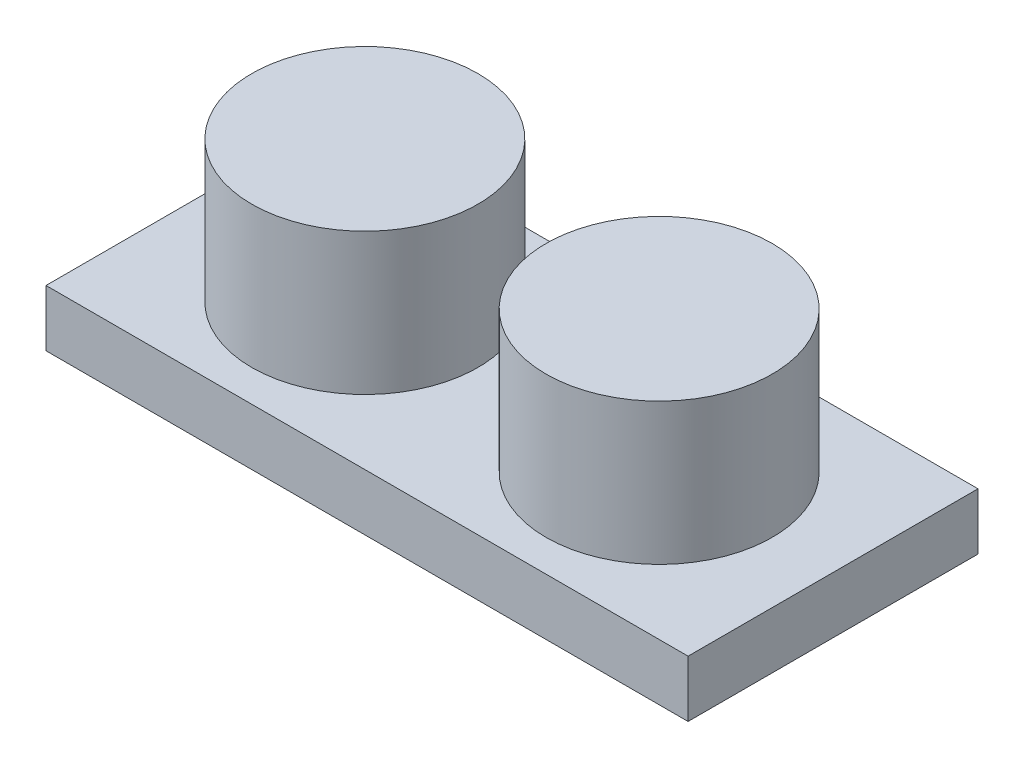
SolidWorks part; units mm, degrees
ref_plane "前基準面" through (0, 0, 0) normal (0, 0, 1) x (1, 0, 0)
ref_plane "上基準面" through (0, 0, 0) normal (0, 1, 0) x (1, 0, 0)
ref_plane "右基準面" through (0, 0, 0) normal (1, 0, 0) x (0, 0, -1)
sketch "草圖1" plane through (0, 0, 0) normal (0, 1, 0) x (1, 0, 0)
  line L0 (0, 10.25) -> (0, -10.25) construction
  line L1 (-22.7, 10.25) -> (22.7, 10.25)
  line L2 (-22.7, 10.25) -> (-22.7, -10.25)
  line L3 (-22.7, -10.25) -> (22.7, -10.25)
  line L4 (22.7, 10.25) -> (22.7, -10.25)
  line L5 (-22.7, 10.25) -> (22.7, -10.25) construction
  line L6 (-22.7, -10.25) -> (22.7, 10.25) construction
  circle A0 centre (-10.4042, 0) radius 8
  circle A1 centre (10.4042, 0) radius 8
  point P0 (0, 0)
  point P10 (-10.4042, 0)
  dimension "D1" = 45.4
  dimension "D2" = 20.5
extrude "填料-伸長3" add sketch "草圖1" along normal blind 4 contours L4 L1 L2 L3 A0 A1 | A0 | A1 region at (0, 0, 0)
extrude "填料-伸長4" add sketch "草圖1<5>" along normal blind 14 contours A0 | A1 region at (-10.4042, 0, 0) region at (10.4042, 0, 0)
sketch "草圖1<5>" plane through (0, 0, 0) normal (0, 1, 0) x (1, 0, 0) same geometry as "草圖1"
